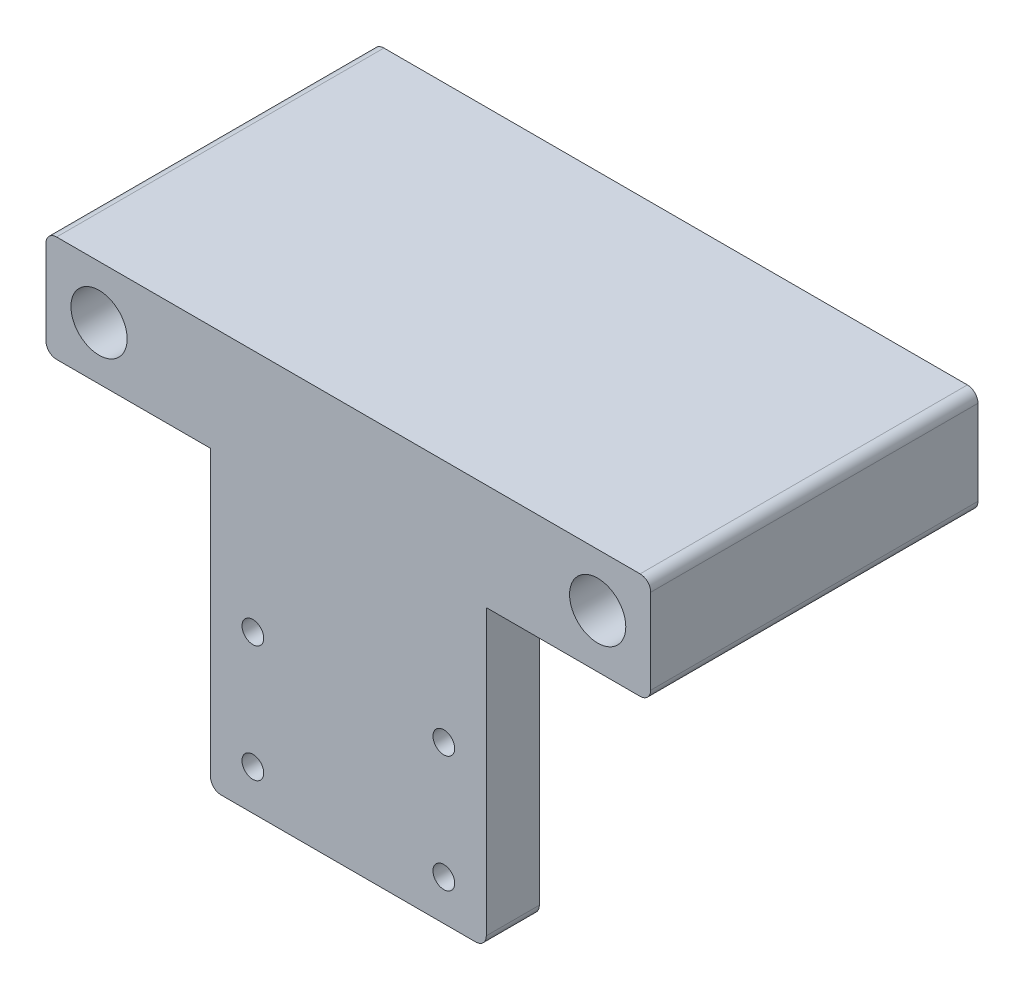
SolidWorks part; units mm, degrees
material "ABS"
ref_plane "Front Plane" through (0, 0, 0) normal (0, 0, 1) x (1, 0, 0)
ref_plane "Top Plane" through (0, 0, 0) normal (0, 1, 0) x (1, 0, 0)
ref_plane "Right Plane" through (0, 0, 0) normal (1, 0, 0) x (0, 0, -1)
sketch "Body Sketch" plane through (0, 0, 0) normal (0, 0, 1) x (1, 0, 0)
  line L0 (0, -5.5) -> (0, -7.3) construction
  line L1 (-11, 20.7) -> (11, 20.7) construction
  line L2 (-11, 20.7) -> (-11, -7.3) construction
  line L3 (-11, -7.3) -> (11, -7.3) construction
  line L4 (11, 20.7) -> (11, -7.3) construction
  line L5 (-11, 20.7) -> (11, -7.3) construction
  line L6 (-11, -7.3) -> (11, 20.7) construction
  line L7 (-9, 5.5) -> (9, 5.5) construction
  line L8 (-9, 5.5) -> (-9, -5.5) construction
  line L9 (-9, -5.5) -> (9, -5.5) construction
  line L10 (9, 5.5) -> (9, -5.5) construction
  line L11 (0, 5.5) -> (0, -5.5) construction
  line L12 (-9, 0) -> (9, 0) construction
  line L13 (-28.5, 18.5) -> (-13, 18.5)
  line L18 (-13, 18.5) -> (-13, -9.3)
  line L19 (-13, -9.3) -> (13, -9.3)
  line L20 (-28.5, -28.5) -> (28.5, -28.5) construction
  line L21 (-28.5, -28.5) -> (-28.5, 28.5)
  line L22 (-28.5, 28.5) -> (28.5, 28.5)
  line L23 (28.5, -28.5) -> (28.5, 28.5)
  line L24 (-28.5, -28.5) -> (28.5, 28.5) construction
  line L25 (-28.5, 28.5) -> (28.5, -28.5) construction
  line L26 (13, -9.3) -> (13, 18.5)
  line L27 (13, 18.5) -> (28.5, 18.5)
  line L30 (-23.5, 23.5) -> (23.5, 23.5) construction
  line L31 (-23.5, 23.5) -> (-23.5, -23.5) construction
  line L32 (-23.5, -23.5) -> (23.5, -23.5) construction
  line L33 (23.5, 23.5) -> (23.5, -23.5) construction
  line L34 (-13, 18.5) -> (13, 18.5)
  circle A0 centre (9, 5.5) radius 1.3 construction
  circle A1 centre (-9, -5.5) radius 1.3 construction
  circle A2 centre (-23.5, 23.5) radius 5 construction
  circle A3 centre (23.5, 23.5) radius 5 construction
  circle A4 centre (0, 0) radius 4 construction
  point P16 (0, 0)
  point P17 (0, 0)
  point P24 (0, 0)
  point P44 (0, -9.3)
  dimension "D1" = 2.6
  dimension "Clearance Hole Diameter" = 10
  dimension "D11" = 8
  dimension "PCB Width" = 22
  dimension "PCB Height" = 28
  dimension "D2" = 11
  dimension "D3" = 18
  dimension "D4" = 1.8
  dimension "D5" = 57
  dimension "D12" = 47
  dimension "Overlap" = 2
  dimension "LateralOverlap" = 2
extrude "PCB Mount" add sketch "Body Sketch" along normal blind 5 contours L18 L27 | L27 region at (0, 23.5, 0) region at (0, 4.6, 0)
extrude "Stepper Offset Mount" add sketch "Body Sketch<6>" against normal blind 25.85 contours L13 L34 L27 L23 L22 L21 region at (0, 23.5, 0)
sketch "Body Sketch<6>" plane through (0, 0, 0) normal (0, 0, 1) x (1, 0, 0) same geometry as "Body Sketch"
hole_wizard "M5 Clearance Hole1" positions "Sketch3" profile "Sketch5" hole size "M5" standard "ANSI Metric" end condition through all
sketch "Sketch3" plane through (0, 0, 5) normal (0, 0, 1) x (1, 0, 0)
  point P0 (-23.5, 23.5)
  point P3 (23.5, 23.5)
sketch "Sketch5" plane through (-23.5, 23.5, 5) normal (1, 0, 0) x (0, -1, 0)
  line L0 (0, 0) -> (0, 30.85)
  line L1 (0, 30.85) -> (2.65, 30.85)
  line L2 (2.65, 30.85) -> (2.65, 0)
  line L5 (2.65, 0) -> (0, 0)
  line L11 (0, -6.35) -> (0, 107.95) construction
  dimension "Thru Hole Dia." = 5.3
  dimension "Thru Hole Depth" = 30.85
hole_wizard "Tap Drill for M2.5x0.45 Tap1" positions "Sketch6" profile "Sketch7" hole size "M2.5x0.45" standard "ANSI Metric" end condition through all
sketch "Sketch6" plane through (0, 0, 5) normal (0, 0, 1) x (1, 0, 0)
  point P0 (-9, 5.5)
  point P3 (-9, -5.5)
  point P6 (9, -5.5)
  point P9 (9, 5.5)
sketch "Sketch7" plane through (-9, 5.5, 5) normal (1, 0, 0) x (0, -1, 0)
  line L0 (0, 0) -> (0, 30.85)
  line L1 (0, 30.85) -> (1.025, 30.85)
  line L2 (1.025, 30.85) -> (1.025, 0)
  line L5 (1.025, 0) -> (0, 0)
  line L11 (0, -6.35) -> (0, 107.95) construction
  dimension "Thru Hole Dia." = 2.05
  dimension "Thru Hole Depth" = 30.85
fillet "Fillet1" radius 1 4 edges at (-28.5, 18.5, -10.425) (-28.5, 28.5, -10.425) (28.5, 18.5, -10.425) (28.5, 28.5, -10.425)
fillet "Fillet2" radius 1 2 edges at (13, -9.3, 2.5) (-13, -9.3, 2.5)
equation "\"D5@Body Sketch\" = 57mm"
equation "\"Clearance Hole Diameter@Body Sketch\" = \"M5_ClearanceDiameter\""
equation "\"ExtrusionStandard\"= 20mm'Size of extrusion used for framing"
equation "\"BaseExtrusionFrameWidth\"= 60mm'Width of the central aluminum extrusion"
equation "\"BaseExtrusionFrameHeight\"= 20mm'Height of the central aluminum extrusion"
equation "\"PlateThickness\"= 15mm'Thickness of the the front and back framing plates"
equation "\"RailHeight\"= 13mm'Total height of the carriage and rail component"
equation "\"WallThickness\"= 3mm'Standard wall thickness"
equation "\"ShaftDiameter\"= 20mm'Outside Diameter of the main yoke shaft"
equation "\"ShaftClearance\"= 1mm'Clearance/gap between the main yoke and non-bearing elements"
equation "\"PlainBearingBoltCircleDiameter\"= ( \"WallThickness\" + \"M3_ClearanceDiameter\" / 2 ) * 2 + \"PlainBearingOD\"'Bolt circle diameter for the plain bearing retainer/mount"
equation "\"PlainBearingBoltcount\"= 5'Number of bolts used in the plain bearing/mount"
equation "\"LeadScrewDiameter\"= 6.35mm'OD of the leadsrew used on the Y axis"
equation "\"LeadScrewHeight\"= 10mm'Height of the center of the Lead screw from bottom of gantry extrusion"
equation "\"LeadScrewNut_FlangeOD\"= 25mm'OD of the lead screw nut flange"
equation "\"LeadScrewNut_BoltCircleDiameter\"= 19mm'Bolt circle diameter needed to mount the leadscrew nut"
equation "\"LeadScrewNut_BoltCount\"= 6'Number of bolts required to mount the leadscrew nut to gantry."
equation "\"X_BeltPitch\"= 2mm'Pitch of the timing belt used on the X axis/main shaft."
equation "\"X_Drive_Teeth\"= 20'Number of teeth used on the X/Main stepper motor pulley"
equation "\"X_Shaft_Teeth\"= 60'Number of teeth on the X/Main shaft pulley"
equation "\"X_Drive_PD\"= ( \"X_Drive_Teeth\" * \"X_BeltPitch\" ) / PI'Pitch Diameter of the X/main motor pulley"
equation "\"X_Shaft_PD\"= ( \"X_Shaft_Teeth\" * \"X_BeltPitch\" ) / PI'Pitch Diameter of the X/main shaft pulley"
equation "\"X_CenterDistance\"= 55mm'Distance between the main shaft and motor pulley centers"
equation "\"GantryLength\"= 150mm'Length of the gantry extrusion/plate"
equation "\"X_MotorPlateThickness\"= 15mm'Thickness of the plate used to hold the X/main motor"
equation "\"X_MotorPlateLength\"= \"X_MotorPlateThickness\" + \"ExtrusionStandard\" * 2'FIXME"
equation "\"X_BeltWidth\" = 9mm'Width of the timing belt used on the X/Main shaft rotary drive"
equation "\"X_PillowLength\"= ( \"WallThickness\" * 4 ) + \"X_RearCollarThickness\" + ( \"X_ThrustBearingThickness\" * 2 ) + \"X_ShaftRotaryBearingThickness\"'Total length of the pillow block used to hold the main shaft"
equation "\"ShaftLength\"= 400mm'Length of the main shaft."
equation "\"PlainBearingOD\"= 31.8mm'OD of the Plain Bearing housing"
equation "\"Y_Drive_Length\"= \"ShaftLength\"'duplicate"
equation "\"Y_Drive_Diameter\"= \"LeadScrewDiameter\"'duplicate"
equation "\"Y_Drive_ThrustBearingOD\"= .5625in'OD of the thrust bearings used to support the leadscrew/Y drive"
equation "\"Y_Drive_ThrustBearingThickness\"= .193in'Thickness of the thrust bearings used to support the leadscrew/Y drive"
equation "\"Y_Drive_ShaftCollarOD\"= .6875in'OD of the collar used to constrain the leadscrew/Y drive"
equation "\"Y_Drive_ShaftCollarThickness\"= .3125in'Thickness of the collar used to constrain the leadscrew/Y drive"
equation "\"Y_Drive_ShaftCollarClearance\"= .375in / 2'Amount of radial clearance needed around the leadscrew/Y shaft collar"
equation "\"calc_Y_Drive_BearingLargestDiameter\"= IIF ( \"Y_Drive_ThrustBearingOD\" > \"Y_Drive_ShaftCollarOD\" , \"Y_Drive_ThrustBearingOD\" , \"Y_Drive_ShaftCollarOD\" )'FIXME - calculated diameter needed for Y drive pillow - needs to account for collar clearance."
equation "\"Y_Drive_BearingBoltCircleDiameter\"= \"calc_Y_Drive_BearingLargestDiameter\" + ( \"Y_Drive_ShaftCollarClearance\" * 2 ) + ( \"WallThickness\" * 2 ) + 2 * 10mm'FIXME - unused?"
equation "\"M3_ClearanceDiameter\"= 8mm'Keepout diameter for M3 holes"
equation "\"M5_ClearanceDiameter\"= 10mm'Keepout Diameter for M5 holes"
equation "\"Y_Drive_CenterDistance\"= 65mm'Center Distance between Y motor drive and leadscrew pulley"
equation "\"Y_Drive_Teeth\"= 20'Number of teeth on the Y/linear stepper pulley"
equation "\"Y_Drive_ShaftTeeth\"= 60'Number of teeth on the Y/linear leadscrew pulley"
equation "\"Y_Drive_BeltWidth\"= 9mm'Width of the belt used on the Y/linear drive"
equation "\"Y_Drive_BeltPitch\"= 2mm'Pitch of the timing belt used on the Y/linear drive"
equation "\"Y_Drive_PD\"= ( \"Y_Drive_Teeth\" * \"Y_Drive_BeltPitch\" ) / PI'Pitch Diameter of the stepper pulley for the Y/linear drive"
equation "\"Y_Drive_ShaftPD\"= ( \"Y_Drive_ShaftTeeth\" * \"Y_Drive_BeltPitch\" ) / PI'Pitch diameter of the pulley on the Y/linear leadscrew"
equation "\"PlainBearingLength\"= 44.8mm'Length of the plain bearing housing"
equation "\"Y_Drive_ShaftBearingThickness\"= .196in'Thickness of the radial bearing used to support the Y leadscrew"
equation "\"Y_Drive_ShaftBearingOD\"= .625in'OD of the radial bearing used to support the Y leadscrew"
equation "\"EncoderMount_BoltWidth\"= 80mm"
equation "\"EncoderMount_BoltRowCount\" = 1"
equation "\"EncoderMount_BoltRowDistance\"= 20mm"
equation "\"EncoderMount_Offset\"= 10mm"
equation "\"Y_Drive_StepperShaftLength\"= 21mm"
equation "\"X_StepperShaftLength\" = 21mm"
equation "\"Y_DriveStepperShaftDiameter\"= 6.35mm"
equation "\"X_StepperShaftDiameter\"= 6.35mm"
equation "\"X_ThrustBearingOD\"= 35mm'OD of the thrust bearing used on the main shaft"
equation "\"X_ThrustBearingID\"= 20mm'ID of the thrust bearing used on the main shaft"
equation "\"X_ThrustBearingThickness\"= 10mm'Thickness of the thrust bearing used on the main shaft"
equation "\"X_RearCollarOD\"= 32mm'OD of the shaft collar of the main shaft"
equation "\"X_RearCollarID\"= 20mm'ID of the shaft collar of the main shaft"
equation "\"X_RearCollarThickness\"= 8mm'Thickness of the collar along the main shaft"
equation "\"X_ShaftRotaryBearingThickness\"= 9mm'Thickness of the radial bearing used on the main shaft"
equation "\"X_ShaftRotaryBearingOD\"= 37mm'OD of the radial bearing used on the main shaft"
equation "\"Pillow_BaseClearance\"= 6mm + \"WallThickness\"'Pillow block base needed to internally mount screws"
equation "\"X_PillowHeight\"= \"Pillow_BaseClearance\" + \"calc_X_PillowRadius\"'Height of the main shaft pillow block base, as measured from the top of the gantry surface"
equation "\"calc_X_PillowRadius\"= IIF ( ( \"X_ThrustBearingOD\" / 2 ) > ( \"X_RearCollarOD\" / 2 * 1.5 ) , \"X_ThrustBearingOD\" / 2 , ( \"X_RearCollarOD\" / 2 ) * 1.5 ) + ( \"WallThickness\" )'Minimum Radius needed for X/main shaft pillow block elements."
equation "\"calc_Y_PillowRadius\"= IIF ( \"Y_Drive_ThrustBearingOD\" / 2 > ( \"Y_Drive_ShaftCollarOD\" / 2 * 1.5 ) , \"Y_Drive_ThrustBearingOD\" / 2 , ( \"Y_Drive_ShaftCollarOD\" / 2 ) * 1.5 )'Minimum radius needed for the Y/linear shaft pillow block elements"
equation "\"Y_PillowHeight\"= \"Pillow_BaseClearance\" + \"calc_Y_PillowRadius\"'Height of the Y/linear pillow block base"
equation "\"Assembly_MainShaftStickout\"= 50mm'Amount of stickout at maximum pitch down (yoke forward)"
equation "\"PCB_Thickness\"= 2.6mm"
